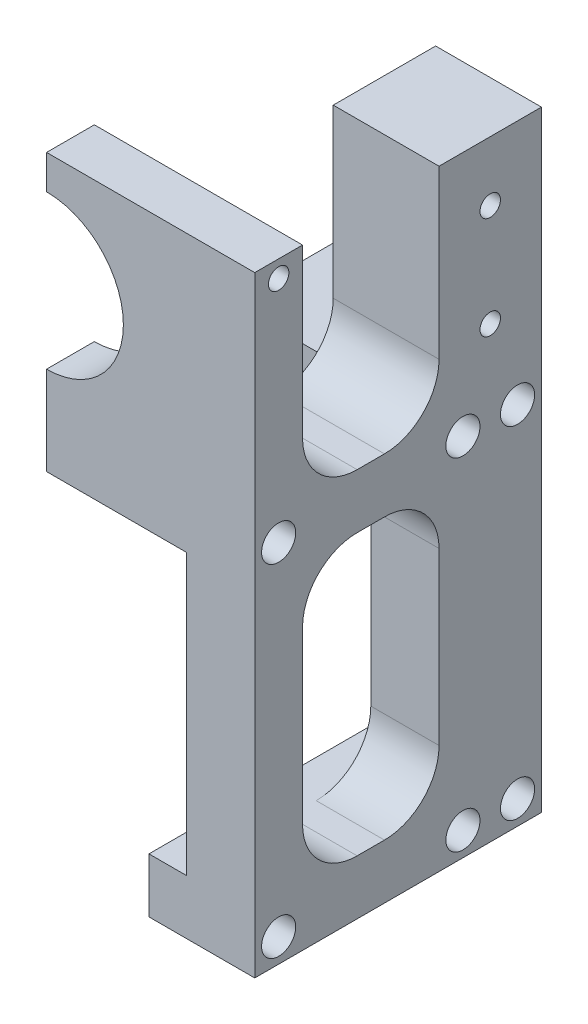
SolidWorks part; units mm, degrees
ref_plane "Front Plane" through (0, 0, 0) normal (0, 0, 1) x (1, 0, 0)
ref_plane "Top Plane" through (0, 0, 0) normal (0, 1, 0) x (1, 0, 0)
ref_plane "Right Plane" through (0, 0, 0) normal (1, 0, 0) x (0, 0, -1)
sketch "Sketch1" plane through (0, 0, 0) normal (0, 0, 1) x (1, 0, 0)
  line L0 (44.45, -0.635) -> (44.45, -10.795)
  line L1 (0, 0) -> (50.8, 0) construction
  line L2 (0, 0) -> (0, 50.8) construction
  line L3 (0, 50.8) -> (50.8, 50.8) construction
  line L4 (50.8, 0) -> (50.8, 50.8) construction
  line L5 (44.45, -10.795) -> (64.135, -10.795)
  line L6 (64.135, -10.795) -> (64.135, 102.87)
  line L10 (44.45, 100.33) -> (44.45, 61.595)
  line L11 (44.45, 61.595) -> (25.4, 61.595)
  line L12 (25.4, 61.595) -> (25.4, 51.435)
  line L13 (25.4, 51.435) -> (51.435, 51.435)
  line L14 (51.435, 51.435) -> (51.435, -0.635)
  line L15 (51.435, -0.635) -> (44.45, -0.635)
  line L17 (25.4, 62.23) -> (25.4, 51.435) construction
  line L18 (6.35, 100.33) -> (44.45, 100.33) construction
  line L19 (6.35, 100.33) -> (6.35, 62.23) construction
  line L20 (6.35, 62.23) -> (44.45, 62.23) construction
  line L21 (44.45, 100.33) -> (44.45, 62.23) construction
  line L22 (44.45, 100.33) -> (44.45, 102.87)
  line L23 (44.45, 102.87) -> (64.135, 102.87)
  point P9 (25.4, 50.8)
  dimension "D1" = 50.8
  dimension "D2" = 0.635
  dimension "D3" = 0.635
  dimension "D4" = 0.635
  dimension "D5" = 6.35
  dimension "D6" = 12.7
  dimension "D7" = 10.16
  dimension "D8" = 10.16
  dimension "D9" = 38.1
  dimension "D10" = 0.635
  dimension "D11" = 2.54
extrude "Boss-Extrude1" add sketch "Sketch1" along normal blind 19.05
sketch "Sketch2" plane through (64.135, 0, 0) normal (1, 0, 0) x (0, 0, -1)
  line L9 (-19.05, 102.87) -> (0, 102.87) construction
  line L10 (-9.525, 72.7075) -> (-9.525, 91.7575) construction
  line L14 (-19.05, 102.87) -> (-19.05, 61.595) construction
  circle A10 centre (-9.525, 91.7575) radius 1.905
  circle A11 centre (-9.525, 72.7075) radius 1.905
  point P3 (-9.525, 102.87)
  point P14 (-19.05, 82.2325)
  point P15 (-9.525, 82.2325)
  dimension "D2" = 3.81
  dimension "D3" = 19.05
extrude "Cut-Extrude1" cut sketch "Sketch2" against normal through all both
sketch "Sketch3" plane through (0, 0, 19.05) normal (0, 0, 1) x (1, 0, 0)
  line L0 (25.4, 96.52) -> (25.4, 102.87)
  line L2 (25.4, 61.595) -> (25.4, 67.945)
  line L3 (25.4, 102.87) -> (44.45, 102.87)
  line L5 (25.4, 96.52) -> (25.4, 82.2325) construction
  line L10 (44.45, -10.795) -> (64.135, -10.795)
  line L11 (64.135, -10.795) -> (64.135, 102.87)
  line L12 (64.135, 102.87) -> (44.45, 102.87)
  line L13 (44.45, 102.87) -> (44.45, 61.595)
  line L14 (44.45, 61.595) -> (25.4, 61.595)
  line L15 (25.4, 61.595) -> (25.4, 51.435)
  line L16 (25.4, 51.435) -> (51.435, 51.435)
  line L17 (51.435, 51.435) -> (51.435, -0.635)
  line L18 (51.435, -0.635) -> (44.45, -0.635)
  line L19 (44.45, -0.635) -> (44.45, -10.795)
  line L20 (44.45, -10.795) -> (64.135, -10.795)
  line L21 (64.135, -10.795) -> (64.135, 102.87)
  line L25 (25.4, 61.595) -> (25.4, 51.435)
  line L26 (25.4, 51.435) -> (51.435, 51.435)
  line L27 (51.435, 51.435) -> (51.435, -0.635)
  line L28 (51.435, -0.635) -> (44.45, -0.635)
  line L29 (44.45, -0.635) -> (44.45, -10.795)
  line L36 (64.135, 102.87) -> (44.45, 102.87)
  arc A0 (25.4, 67.945) -> (25.4, 96.52) centre (25.4, 82.2325) ccw
  dimension "D2" = 28.575
  dimension "D1" = 0
extrude "Boss-Extrude2" add sketch "Sketch3" along normal blind 8.89 from offset 25.4 separate body
sketch "Sketch4" [suppressed] plane through (0, 0, 0) normal (0, 0, -1) x (-1, 0, 0)
  line L10 (-44.45, -0.635) -> (-51.435, -0.635)
  line L11 (-51.435, -0.635) -> (-51.435, 51.435)
  line L12 (-51.435, 51.435) -> (-25.4, 51.435)
  line L13 (-25.4, 51.435) -> (-25.4, 61.595)
  line L14 (-25.4, 102.87) -> (-44.45, 102.87)
  line L15 (-25.4, 102.87) -> (-44.45, 102.87)
  line L16 (-44.45, 102.87) -> (-64.135, 102.87)
  line L17 (-64.135, 102.87) -> (-64.135, -10.795)
  line L18 (-64.135, -10.795) -> (-44.45, -10.795)
  line L19 (-44.45, -10.795) -> (-44.45, -0.635)
  line L30 (-44.45, -0.635) -> (-51.435, -0.635)
  line L31 (-51.435, -0.635) -> (-51.435, 51.435)
  line L32 (-51.435, 51.435) -> (-25.4, 51.435)
  line L33 (-25.4, 51.435) -> (-25.4, 61.595)
  line L37 (-64.135, 102.87) -> (-64.135, -10.795)
  line L38 (-64.135, -10.795) -> (-44.45, -10.795)
  line L39 (-44.45, -10.795) -> (-44.45, -0.635)
  line L41 (-25.4, 96.52) -> (-25.4, 102.87)
  line L42 (-25.4, 96.52) -> (-25.4, 102.87)
  line L43 (-25.4, 61.595) -> (-25.4, 67.945)
  line L44 (-25.4, 61.595) -> (-25.4, 67.945)
  line L45 (-44.45, 102.87) -> (-64.135, 102.87)
  arc A1 (-25.4, 96.52) -> (-25.4, 67.945) centre (-25.4, 82.2325) ccw
  arc A2 (-25.4, 96.52) -> (-25.4, 67.945) centre (-25.4, 82.2325) ccw
  dimension "D1" = 0
extrude "Boss-Extrude3" [suppressed] add sketch "Sketch4" along normal blind 8.89 from offset 25.4 separate body
sketch "Sketch5" plane through (0, 0, 53.34) normal (0, 0, 1) x (1, 0, 0)
  line L5 (64.135, -10.795) -> (64.135, 102.87) construction
  line L6 (44.45, -0.635) -> (64.135, -0.635)
  line L7 (44.45, -0.635) -> (44.45, -10.795)
  line L8 (44.45, -10.795) -> (64.135, -10.795)
  line L9 (64.135, -0.635) -> (64.135, -10.795)
  line L10 (44.45, 61.595) -> (64.135, 61.595)
  line L11 (44.45, 61.595) -> (44.45, 51.435)
  line L12 (44.45, 51.435) -> (64.135, 51.435)
  line L13 (64.135, 61.595) -> (64.135, 51.435)
  line L14 (25.4, 51.435) -> (51.435, 51.435) construction
  dimension "D1" = 19.685
  dimension "D2" = 10.16
extrude "Boss-Extrude4" add sketch "Sketch5" against normal up to surface (34.29 mm away) up to face at (45.974, 40.894, 19.05)
sketch "Sketch6" plane through (64.135, 0, 0) normal (1, 0, 0) x (0, 0, -1)
  line L0 (-14.605, 57.15) -> (-4.445, 57.15) construction
  line L1 (-4.445, 57.15) -> (-4.445, -6.35) construction
  line L2 (-4.445, -6.35) -> (-14.605, -6.35) construction
  line L3 (-14.605, -6.35) -> (-14.605, 57.15) construction
  line L4 (-19.05, 61.595) -> (0, 61.595) construction
  line L5 (0, 61.595) -> (0, -10.795) construction
  circle A0 centre (-14.605, 57.15) radius 3.175
  circle A1 centre (-4.445, 57.15) radius 3.175
  circle A2 centre (-14.605, -6.35) radius 3.175
  circle A3 centre (-4.445, -6.35) radius 3.175
  point P12 (-9.525, 61.595)
  point P13 (-9.525, 57.15)
  point P18 (0, 25.4)
  point P19 (-4.445, 25.4)
  dimension "D3" = 6.35
  dimension "D1" = 63.5
  dimension "D2" = 10.16
extrude "Cut-Extrude2" cut sketch "Sketch6" against normal through all both
sketch "Sketch7" [suppressed] plane through (64.135, 0, 0) normal (1, 0, 0) x (0, 0, -1)
  line L0 (-53.34, -10.795) -> (0, -10.795) construction
  line L1 (-53.34, 102.87) -> (-19.05, 102.87)
  line L2 (-53.34, 102.87) -> (-53.34, -10.795)
  line L3 (-53.34, -10.795) -> (-19.05, -10.795)
  line L4 (-19.05, 102.87) -> (-19.05, -10.795)
  line L6 (-19.05, -0.635) -> (-19.05, 51.435) construction
extrude "Cut-Extrude3" [suppressed] cut sketch "Sketch7" against normal through all both
sketch "Sketch8" [suppressed] plane through (0, 0, -34.29) normal (0, 0, -1) x (-1, 0, 0)
  line L0 (-64.135, 102.87) -> (-64.135, -10.795) construction
  line L1 (-44.45, 61.595) -> (-64.135, 61.595)
  line L2 (-44.45, 61.595) -> (-44.45, 51.435)
  line L3 (-44.45, 51.435) -> (-64.135, 51.435)
  line L4 (-64.135, 61.595) -> (-64.135, 51.435)
  line L5 (-51.435, 51.435) -> (-25.4, 51.435) construction
  line L6 (-44.45, -10.795) -> (-64.135, -10.795)
  line L7 (-44.45, -10.795) -> (-44.45, -0.635)
  line L8 (-44.45, -0.635) -> (-64.135, -0.635)
  line L9 (-64.135, -10.795) -> (-64.135, -0.635)
  dimension "D1" = 19.685
  dimension "D2" = 10.16
extrude "Boss-Extrude5" [suppressed] add sketch "Sketch8" against normal up to surface (34.29 mm away)
sketch "Sketch9" plane through (64.135, 0, 0) normal (1, 0, 0) x (0, 0, -1)
  line L0 (-48.895, 57.15) -> (-48.895, -6.35) construction
  line L1 (-48.895, -6.35) -> (-14.605, -6.35) construction
  line L2 (-14.605, -6.35) -> (-14.605, 57.15) construction
  line L3 (-14.605, 57.15) -> (-48.895, 57.15) construction
  line L4 (-53.34, 102.87) -> (-44.45, 102.87) construction
  circle A0 centre (-48.895, 57.15) radius 3.175
  circle A1 centre (-48.895, -6.35) radius 3.175
  circle A2 centre (-14.605, 57.15) radius 3.175 construction
  point P12 (-48.895, 102.87)
extrude "Cut-Extrude4" cut sketch "Sketch9" against normal through all both
sketch "Sketch10" [suppressed] plane through (64.135, 0, 0) normal (1, 0, 0) x (0, 0, -1)
  line L0 (29.845, 57.15) -> (-4.445, 57.15) construction
  line L1 (-4.445, 57.15) -> (-4.445, -6.35) construction
  line L2 (-4.445, -6.35) -> (29.845, -6.35) construction
  line L3 (29.845, -6.35) -> (29.845, 57.15) construction
  line L4 (34.29, 102.87) -> (25.4, 102.87) construction
  circle A0 centre (29.845, 57.15) radius 3.175
  circle A1 centre (29.845, -6.35) radius 3.175
  circle A2 centre (-4.445, 57.15) radius 3.175 construction
  point P10 (29.845, 102.87)
extrude "Cut-Extrude5" [suppressed] cut sketch "Sketch10" against normal through all both
fillet "Fillet1" radius 10.16 6 edges at (54.2925, 61.595, 44.45) (54.2925, 61.595, 19.05) (57.785, -0.635, 19.05) (57.785, -0.635, 44.45) (57.785, 51.435, 19.05) (57.785, 51.435, 44.45)
fillet "Fillet2" [suppressed] radius 6.985
sketch "Sketch11" [suppressed] plane through (64.135, 0, 0) normal (1, 0, 0) x (0, 0, -1)
  line L0 (29.845, 99.695) -> (29.845, 57.15) construction
  line L1 (34.29, 96.52) -> (34.29, 102.87) construction
  circle A0 centre (29.845, 99.695) radius 1.905
  circle A2 centre (-9.525, 91.7575) radius 1.905 construction
  point P7 (34.29, 99.695)
extrude "Cut-Extrude6" [suppressed] cut sketch "Sketch11" against normal through all both
sketch "Sketch14" plane through (64.135, 0, 0) normal (1, 0, 0) x (0, 0, -1)
  line L0 (-53.34, 102.87) -> (-53.34, 96.52) construction
  line L1 (-48.895, 99.695) -> (-48.895, 57.15) construction
  circle A0 centre (-48.895, 99.695) radius 1.905
  circle A2 centre (-9.525, 91.7575) radius 1.905 construction
  point P9 (-53.34, 99.695)
extrude "Cut-Extrude8" cut sketch "Sketch14" against normal through all both and the other way through all contours A0
